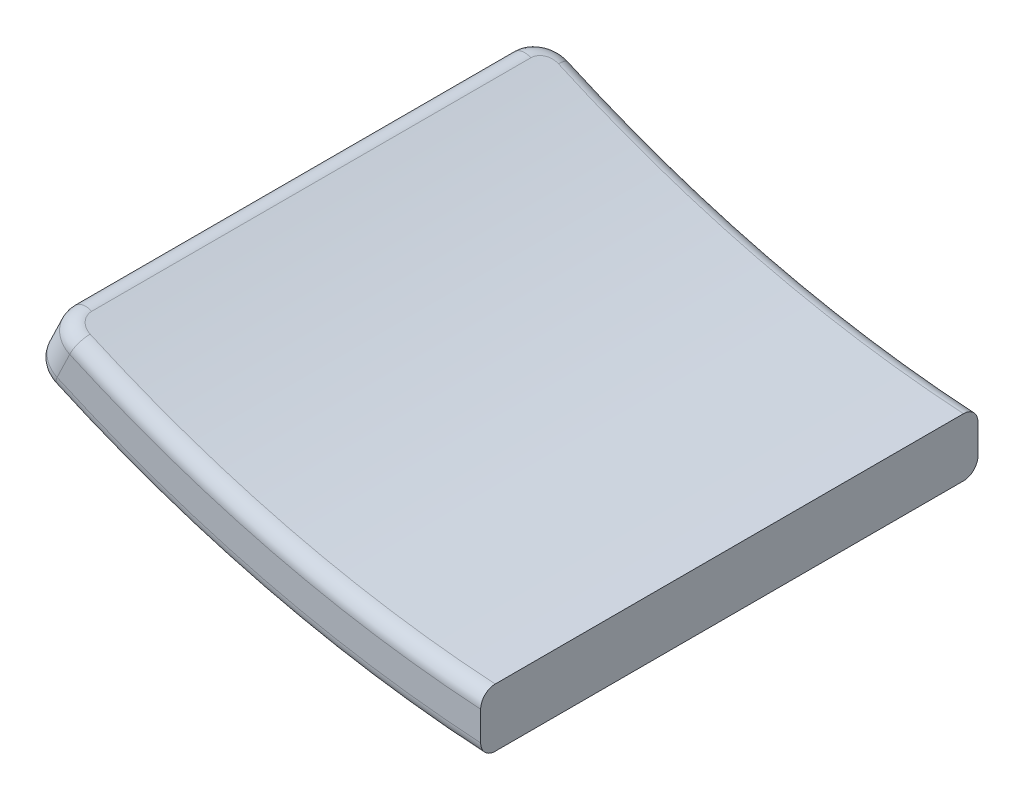
SolidWorks part; units mm, degrees
material "Polyurethane Foam Flexible"
ref_plane "Front Plane" through (0, 0, 0) normal (0, 0, 1) x (1, 0, 0)
ref_plane "Top Plane" through (0, 0, 0) normal (0, 1, 0) x (1, 0, 0)
ref_plane "Right Plane" through (0, 0, 0) normal (1, 0, 0) x (0, 0, -1)
sketch "Sketch1" plane through (0, 0, 0) normal (0, 0, 1) x (1, 0, 0)
  line L0 (-50.8051, 197.3186) -> (-50.8, 146.4209)
  line L1 (-427.4709, 295.7304) -> (-449.4633, 249.9377)
  line L2 (-50.8, -204.8629) -> (-50.8, 160.2621) construction
  arc A0 (-427.4709, 295.7304) -> (-0.043, 195.3653) centre (13.752, 1214.4469) ccw construction
  arc A1 (-427.4709, 295.7304) -> (-50.8051, 197.3186) centre (13.752, 1214.4469) ccw
  arc A2 (-449.4633, 249.9377) -> (-50.8, 146.4209) centre (13.752, 1214.4469) ccw
  arc A3 (-449.4633, 249.9377) -> (-0.7306, 144.57) centre (13.752, 1214.4469) ccw construction
  arc A4 (-427.4709, 295.7304) -> (-0.043, 195.3653) centre (13.752, 1214.4469) ccw construction
  point P5 (-50.8, 146.5048)
  point P6 (-50.8, 146.4209)
  point P7 (-50.8, 197.3186)
  dimension "D2" = 50.8
extrude "Boss-Extrude1" add sketch "Sketch1" against normal up to surface (434.6 mm away)
fillet "Fillet1" radius 25.4 2 edges at (-438.4671, 272.8341, 0) (-438.4671, 272.8341, -434.6)
fillet "Fillet2" radius 12.7 10 edges at (-242.8475, 175.6962, -434.6) (-444.4398, 247.5412, -425.0671) (-449.4633, 249.9377, -217.3) (-440.85, 245.8482, -5.5643) (-242.8475, 175.6962, 0) (-418.8565, 291.6428, -429.0358) (-231.5721, 225.2383, -434.6) (-231.5721, 225.2383, 0) (-422.4471, 293.3346, -9.5329) (-427.4709, 295.7304, -217.3)
